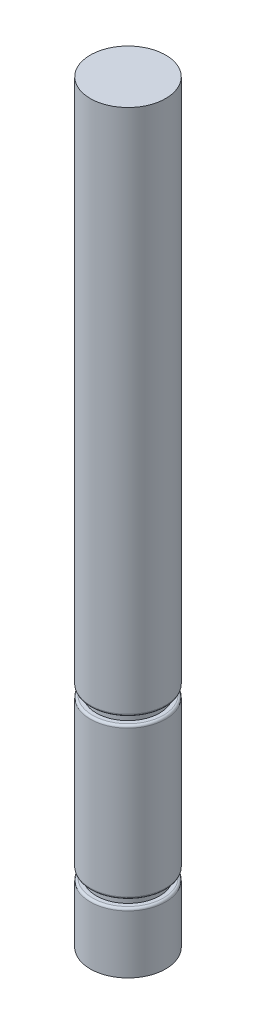
SolidWorks part; units mm, degrees
ref_plane "Front Plane" through (0, 0, 0) normal (0, 0, 1) x (1, 0, 0)
ref_plane "Top Plane" through (0, 0, 0) normal (0, 1, 0) x (1, 0, 0)
ref_plane "Right Plane" through (0, 0, 0) normal (1, 0, 0) x (0, 0, -1)
sketch "Sketch1" plane through (0, 0, 0) normal (0, 1, 0) x (1, 0, 0)
  circle A0 centre (0, 0) radius 5
  dimension "D1" = 10
extrude "Boss-Extrude1" add sketch "Sketch1" along normal blind 100
sketch "Sketch2" plane through (0, 0, 0) normal (0, 1, 0) x (1, 0, 0)
  circle A0 centre (0, 0) radius 5 construction
  circle A1 centre (0, 0) radius 5
  circle A2 centre (0, 0) radius 4.2
  dimension "D1" = 0.8
extrude "Cut-Extrude1" cut sketch "Sketch2" against normal blind 1 from offset 30
fillet "Fillet1" radius 0.3 2 edges at (0, 30, 5) (0, 29, 5)
extrude "Cut-Extrude2" cut sketch "Sketch2<2>" along normal blind 1 from offset 8
sketch "Sketch2<2>" plane through (0, 0, 0) normal (0, 1, 0) x (1, 0, 0) same geometry as "Sketch2"
fillet "Fillet2" radius 0.3 2 edges at (0, 8, 5) (0, 9, 5)
